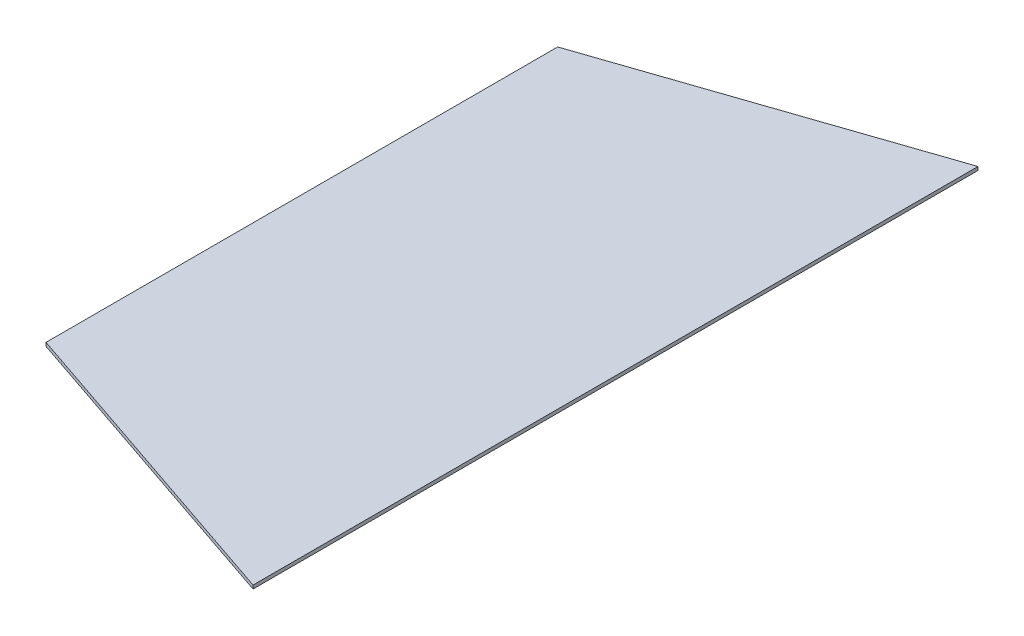
SolidWorks part; units mm, degrees
ref_plane "Front Plane" through (0, 0, 0) normal (0, 0, 1) x (1, 0, 0)
ref_plane "Top Plane" through (0, 0, 0) normal (0, 1, 0) x (1, 0, 0)
ref_plane "Right Plane" through (0, 0, 0) normal (1, 0, 0) x (0, 0, -1)
sketch "Sketch1" plane through (0, 0, 0) normal (0, 1, 0) x (1, 0, 0)
  line L1 (-211.5872, 61.4747) -> (296.4128, 61.4747)
  line L2 (-211.5872, 61.4747) -> (-211.5872, -466.8453)
  line L3 (-211.5872, -466.8453) -> (296.4128, -466.8453)
  line L4 (296.4128, 61.4747) -> (296.4128, -466.8453)
  dimension "D1" = 508
  dimension "D2" = 528.32
extrude "Boss-Extrude1" add sketch "Sketch1" along normal blind 2.54
sketch "Sketch2" plane through (0, 2.54, 0) normal (0, 1, 0) x (1, 0, 0)
  line L0 (296.4128, -466.8453) -> (-211.5872, -294.1253)
  line L2 (-211.5872, 61.4747) -> (-211.5872, -466.8453) construction
  line L3 (-211.5872, -294.1253) -> (-211.5872, -466.8453)
  line L4 (-211.5872, -466.8453) -> (296.4128, -466.8453)
  line L5 (296.4128, 61.4747) -> (-211.5872, -111.2453)
  line L6 (-211.5872, -111.2453) -> (-211.5872, 61.4747)
  line L7 (296.4128, 61.4747) -> (-211.5872, 61.4747) construction
  line L8 (-211.5872, 61.4747) -> (296.4128, 61.4747)
  dimension "D1" = 172.72
  dimension "D2" = 172.72
extrude "Cut-Extrude1" cut sketch "Sketch2" against normal blind 2.54
sketch "Sketch5" plane through (0, 2.54, 0) normal (0, 1, 0) x (1, 0, 0)
  line L6 (67.8128, -16.2493) -> (-211.5872, -111.2453)
  line L7 (-211.5872, -111.2453) -> (296.4128, 61.4747) construction
  line L8 (-211.5872, -111.2453) -> (-211.5872, -294.1253)
  line L9 (-211.5872, -294.1253) -> (67.8128, -389.1213)
  line L10 (296.4128, -466.8453) -> (-211.5872, -294.1253) construction
  line L11 (67.8128, -389.1213) -> (67.8128, -16.2493)
  dimension "D1" = 279.4
extrude "Cut-Extrude4" cut sketch "Sketch5" against normal blind 2.54
